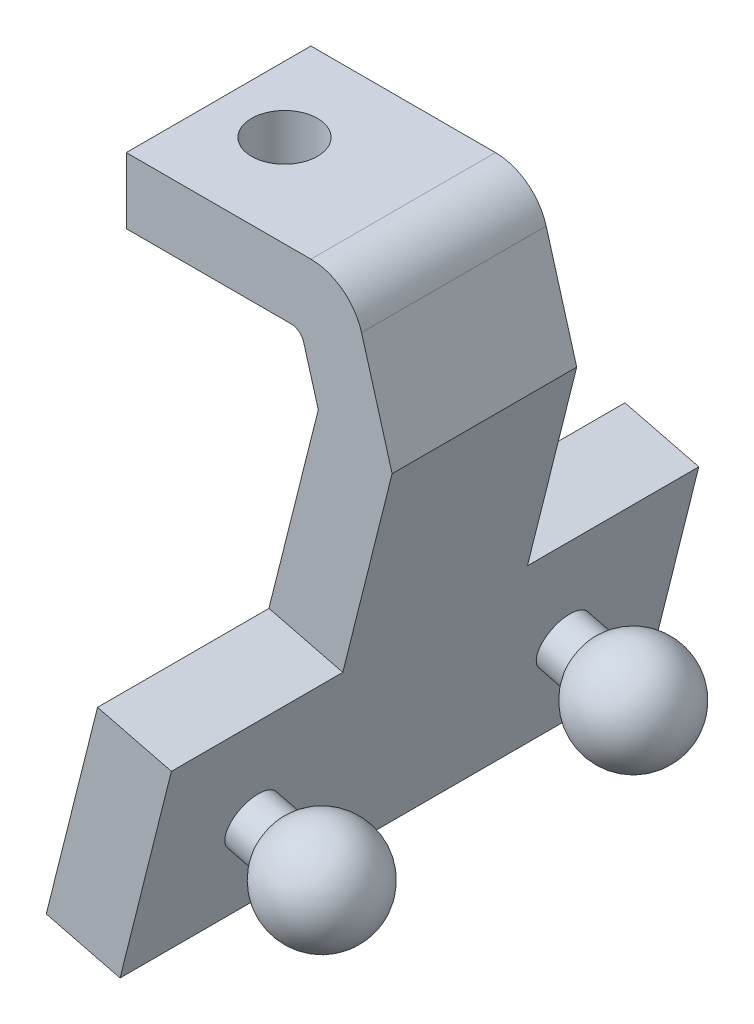
SolidWorks part; units mm, degrees
ref_plane "前视基准面" through (0, 0, 0) normal (0, 0, 1) x (1, 0, 0)
ref_plane "上视基准面" through (0, 0, 0) normal (0, 1, 0) x (1, 0, 0)
ref_plane "右视基准面" through (0, 0, 0) normal (1, 0, 0) x (0, 0, -1)
other "Configuration Table"
sketch "草图1" plane through (0, 0, 0) normal (0, 0, 1) x (1, 0, 0)
  line L0 (0, 0) -> (6.2454, 0)
  line L1 (6.7262, -0.3628) -> (7.2802, -2.304)
  line L2 (7.2802, -2.304) -> (3.4648, -17.5228)
  line L3 (3.4648, -17.5228) -> (6.2649, -18.2248)
  line L4 (6.2649, -18.2248) -> (10.0803, -3.006)
  line L5 (10.0803, -3.006) -> (8.9232, 1.0488)
  line L6 (0, 2.5) -> (7, 2.5)
  line L7 (0, 0) -> (0, 2.5)
  arc A0 (6.2454, 0) -> (6.7262, -0.3628) centre (6.2454, -0.5) cw
  arc A1 (8.9232, 1.0488) -> (7, 2.5) centre (7, 0.5) ccw
  dimension "D1" = 7
  dimension "D3" = 2
  dimension "D6" = 0.5
  dimension "D2" = 2.5
  dimension "D4" = 150
  dimension "D5" = 2.5
extrude "凸台-拉伸1" add sketch "草图1" along normal mid plane 7
sketch "草图2" plane through (0, 0, 0) normal (0, -1, 0) x (1, 0, 0)
  circle A0 centre (2.5, 0) radius 1.25
  dimension "D1" = 2.5
  dimension "D2" = 2.5
extrude "切除-拉伸3" cut sketch "草图2" against normal blind 5.5
sketch "草图3" plane through (10.1932, -2.5554, 0) normal (0.97, -0.2432, 0) x (0, 0, -1)
  line L0 (-3.5, -16.1542) -> (3.5, -16.1542) construction
  line L1 (-10, -8.1542) -> (10, -8.1542)
  line L2 (-10, -8.1542) -> (-10, -16.1542)
  line L3 (-10, -16.1542) -> (10, -16.1542)
  line L4 (10, -8.1542) -> (10, -16.1542)
  line L5 (-10, -8.1542) -> (10, -16.1542) construction
  line L6 (-10, -16.1542) -> (10, -8.1542) construction
  point P0 (0, -12.1542)
  dimension "D1" = 20
  dimension "D2" = 8
extrude "凸台-拉伸2" add sketch "草图3" against normal up to vertex (2.8868 mm away) up to point (3.4648, -17.5228, -3.5)
sketch "草图4" plane through (10.1932, -2.5554, 0) normal (0.97, -0.2432, 0) x (0, 0, -1)
  circle A0 centre (-5.9058, -12.4388) radius 1
  point P2 (-5.9058, -12.4388)
  dimension "D1" = 2
extrude "凸台-拉伸3" add sketch "草图4" along normal blind 1
ref_axis "基准轴1" through (8.0811, -14.8496, 5.9058) along (-0.97, 0.2432, 0)
ref_plane "基准面1" through (-3.0248, -12.0654, 0) normal (0.2432, 0.97, 0) x (-0.97, 0.2432, 0)
sketch "草图5" plane through (-3.0248, -12.0654, 0) normal (0.2432, 0.97, 0) x (-0.97, 0.2432, 0)
  line L0 (-11.5087, 5.9058) -> (-15.2407, 5.9058)
  line L1 (-11.5087, 6.9058) -> (-11.5087, 4.9058) construction
  line L2 (-11.5087, 5.9058) -> (-11.5087, 6.9058)
  arc A0 (-11.5087, 6.9058) -> (-15.2407, 5.9058) centre (-13.2407, 5.9058) ccw
  dimension "D1" = 4
revolve "旋转1" add sketch "草图5" angle 360 about L0
mirror "镜向1" about plane through (0, 0, 0) normal (0, 0, 1) of "凸台-拉伸3", "旋转1"
